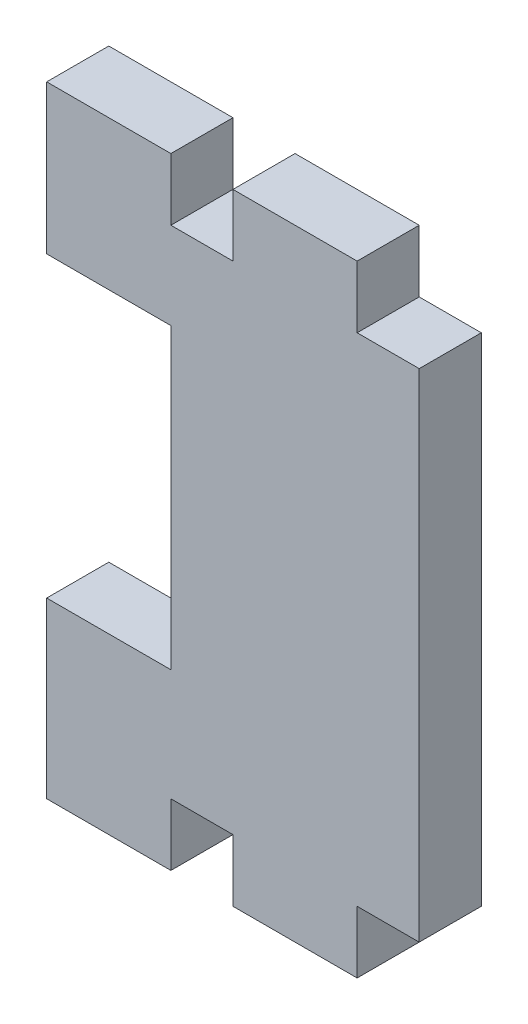
SolidWorks part; units mm, degrees
ref_plane "Plan de face" through (0, 0, 0) normal (0, 0, 1) x (1, 0, 0)
ref_plane "Plan de dessus" through (0, 0, 0) normal (0, 1, 0) x (1, 0, 0)
ref_plane "Plan de droite" through (0, 0, 0) normal (1, 0, 0) x (0, 0, -1)
sketch "Esquisse1" plane through (0, 0, 0) normal (0, 0, 1) x (1, 0, 0)
  line L0 (0, 20) -> (30, 20) construction
  line L1 (10, 0) -> (15, 0)
  line L2 (0, 0) -> (0, 9)
  line L3 (10, 40) -> (15, 40)
  line L4 (30, 0) -> (30, 40)
  line L5 (25, 40) -> (30, 40)
  line L6 (0, 40) -> (0, 45)
  line L7 (0, 45) -> (10, 45)
  line L8 (10, 40) -> (10, 45)
  line L9 (25, 0) -> (30, 0)
  line L10 (15, 40) -> (15, 45)
  line L11 (15, 45) -> (25, 45)
  line L12 (25, 40) -> (25, 45)
  line L13 (25, 0) -> (25, -5)
  line L14 (15, -5) -> (25, -5)
  line L15 (15, 0) -> (15, -5)
  line L16 (10, 0) -> (10, -5)
  line L17 (0, -5) -> (10, -5)
  line L18 (0, 0) -> (0, -5)
  line L19 (0, 33) -> (0, 40)
  line L20 (0, 9) -> (10, 9)
  line L22 (0, 33) -> (10, 33)
  line L23 (10, 9) -> (10, 33)
  dimension "D1" = 40
  dimension "D2" = 30
  dimension "D3" = 10
  dimension "D4" = 5
  dimension "D5" = 5
  dimension "D6" = 10
  dimension "D7" = 9
  dimension "D8" = 24
extrude "Boss.-Extru.1" add sketch "Esquisse1" along normal blind 5
